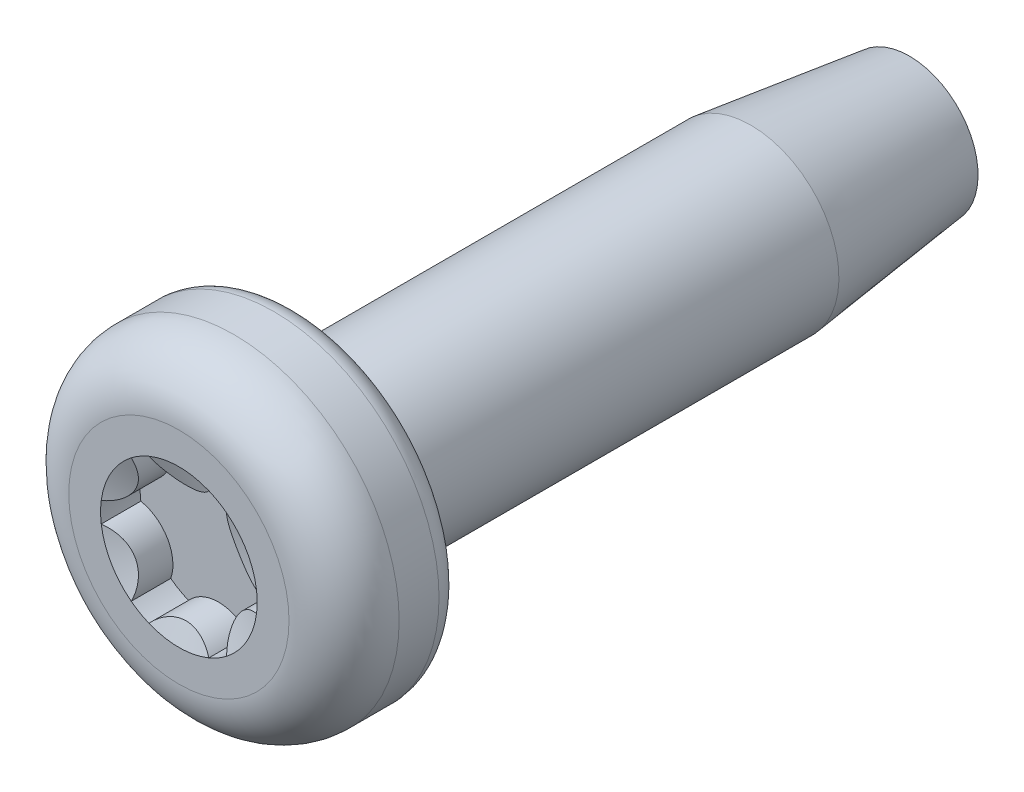
SolidWorks part; units mm, degrees
material "Alloy Steel"
ref_plane "Front" through (0, 0, 0) normal (0, 0, 1) x (1, 0, 0)
ref_plane "Top" through (0, 0, 0) normal (0, 1, 0) x (1, 0, 0)
ref_plane "Right" through (0, 0, 0) normal (1, 0, 0) x (0, 0, -1)
ref_axis "Central Axis" through (0, 0, -94.3109) along (0, 0, 1)
sketch "Sketch17" plane through (0, 0, 0) normal (1, 0, 0) x (0, 0, -1)
  line L1 (0, 0) -> (12.7, 0)
  line L2 (0, 0) -> (0, 1.8288)
  line L3 (0, 1.8288) -> (9.4082, 1.8288)
  line L4 (12.7, 0) -> (12.7, 1.4246)
  line L5 (11.6027, 1.5593) -> (10.5054, 1.6941)
  line L6 (10.5054, 1.6941) -> (10.5054, 1.8288) construction
  line L7 (11.6027, 1.5593) -> (12.7, 1.4246)
  line L8 (10.5054, 1.6941) -> (9.4082, 1.8288)
  line L9 (9.4082, 1.8288) -> (12.7, 1.8288) construction
  line L10 (12.7, 1.8288) -> (12.7, 1.4246) construction
  line L11 (12.7, 0) -> (13.8055, 0) construction
  line L12 (12.7, -1.778) -> (12.7, 1.778) construction
  point P5 (12.7, 1.778)
  point P16 (12.7, 0)
  dimension "Body Length" = 12.7
  dimension "D2" = 2.1946
  dimension "D1" = 7
  dimension "Decimal Equivilent" = 3.556
  dimension "Dia" = 3.6576
revolve "Revolve1" add sketch "Sketch17" angle 360 about L11
sketch "Sketch1" plane through (0, 0, 0) normal (0, 0, 1) x (1, 0, 0)
  circle A0 centre (0, 0) radius 3.429
  dimension "Head Dia" = 6.858
extrude "Extrude3" add sketch "Sketch1" along normal blind 2.4638
sketch "Sketch11" plane through (0, 0, 0) normal (1, 0, 0) x (0, 0, -1)
  line L2 (-2.4638, 3.429) -> (-2.4638, -3.429) construction
  line L4 (0, 3.429) -> (-2.4638, 3.429) construction
  line L5 (-1.3208, 3.429) -> (-0.4928, 3.429)
  line L6 (0, -3.429) -> (0, 3.429) construction
  line L7 (-2.4638, 3.429) -> (-2.4638, 2.286) construction
  line L8 (-2.4638, 1.143) -> (-2.4638, 0) construction
  line L9 (-2.4638, 2.286) -> (-2.4638, 1.143) construction
  line L10 (-2.4638, 2.286) -> (-2.7178, 2.286)
  line L11 (0, 0) -> (-2.4638, 0) construction
  line L12 (-2.7178, 2.286) -> (-2.7178, 3.683)
  line L13 (-2.7178, 3.683) -> (0.254, 3.683)
  line L14 (0.254, 3.683) -> (0.254, 2.9362)
  line L15 (0.254, 2.9362) -> (0, 2.9362)
  arc A0 (-2.4638, 2.286) -> (-1.3208, 3.429) centre (-1.3208, 2.286) cw
  arc A1 (-0.4928, 3.429) -> (0, 2.9362) centre (-0.4928, 2.9362) cw
  dimension "D1" = 0.4928
  dimension "D2" = 0.254
  dimension "D3" = 0.254
revolve "Cut-Revolve3" cut sketch "Sketch11" angle 360 about L11
sketch "Sketch12" plane through (0, 0, 2.4638) normal (0, 0, 1) x (1, 0, 0)
  line L0 (0, 0) -> (0, 1.2192) construction
  line L1 (0, 1.2192) -> (0, 1.6256) construction
  line L2 (0, 0) -> (-0.8128, 1.4078) construction
  line L3 (-0.8128, 1.4078) -> (0.8128, 1.4078) construction
  line L4 (0.8128, 1.4078) -> (0, 0) construction
  line L5 (0.6221, 1.5019) -> (0, 0) construction
  line L6 (0, 0) -> (0.8128, 1.4078) construction
  circle A0 centre (0, 0) radius 1.6256 construction
  circle A2 centre (0, 0) radius 1.4224 construction
  circle A3 centre (0, 0) radius 1.2192 construction
  arc A4 (0.8128, 1.4078) -> (0.6221, 1.5019) centre (0, 0) ccw
  arc A5 (-0.8128, 1.4078) -> (-0.6221, 1.5019) centre (0, 0) cw
  arc A6 (-0.6221, 1.5019) -> (0.6221, 1.5019) centre (0, 2.0451) ccw
  arc A7 (0.8128, 1.4078) -> (0.9896, 1.2897) centre (0, 0) cw
  arc A8 (0.9896, 1.2897) -> (1.6117, 0.2122) centre (1.7711, 1.0225) ccw
  arc A9 (1.6256, 0) -> (1.6117, 0.2122) centre (0, 0) ccw
  arc A10 (1.6256, 0) -> (1.6117, -0.2122) centre (0, 0) cw
  arc A11 (1.6117, -0.2122) -> (0.9896, -1.2897) centre (1.7711, -1.0225) ccw
  arc A12 (0.8128, -1.4078) -> (0.9896, -1.2897) centre (0, 0) ccw
  arc A13 (0.8128, -1.4078) -> (0.6221, -1.5019) centre (0, 0) cw
  arc A14 (0.6221, -1.5019) -> (-0.6221, -1.5019) centre (0, -2.0451) ccw
  arc A15 (-0.8128, -1.4078) -> (-0.6221, -1.5019) centre (0, 0) ccw
  arc A16 (-0.8128, -1.4078) -> (-0.9896, -1.2897) centre (0, 0) cw
  arc A17 (-0.9896, -1.2897) -> (-1.6117, -0.2122) centre (-1.7711, -1.0225) ccw
  arc A18 (-1.6256, 0) -> (-1.6117, -0.2122) centre (0, 0) ccw
  arc A19 (-1.6256, 0) -> (-1.6117, 0.2122) centre (0, 0) cw
  arc A20 (-1.6117, 0.2122) -> (-0.9896, 1.2897) centre (-1.7711, 1.0225) ccw
  arc A21 (-0.8128, 1.4078) -> (-0.9896, 1.2897) centre (0, 0) ccw
  point P4 (0, 1.4224)
  dimension "Torx Size" = 3.2512
  dimension "D1" = 2.4384
  dimension "D2" = 7.5
  dimension "D3" = 6
extrude "Cut-Extrude1" cut sketch "Sketch12" against normal blind 0.8213
sketch "Sketch25" plane through (0, 0, 2.4638) normal (0, 0, 1) x (1, 0, 0)
  circle A0 centre (0, 0) radius 1.6256
  circle A2 centre (0, 0) radius 1.6256 construction
extrude "Cut-Extrude7" cut sketch "Sketch25" against normal through all draft 70
sketch "Sketch19" plane through (0, 0, 0) normal (1, 0, 0) x (0, 0, -1)
  line L0 (6.35, 1.8288) -> (6.35, -1.8288) construction
  line L3 (0, 0) -> (12.7, 0) construction
  line L4 (12.7, 1.8288) -> (12.7, -1.8288) construction
  point P0 (-2.4638, 2.286)
  point P1 (0, 2.9362)
  point P2 (6.35, 0)
sketch "Sketch26" plane through (0, 0, 1.6425) normal (0, 0, 1) x (1, 0, 0)
  line L0 (0, 0) -> (1.1495, -1.1495) construction
  circle A0 centre (0, 0) radius 1.6256 construction
  point P0 (1.1495, -1.1495)
  dimension "D1" = 45
ref_axis "Center Axis 1" through (0, 0, 0) along (0, 0, -1)
split "Split1" [suppressed] bodies to split 157
sketch "Sketch23" [suppressed] plane through (0, 0, -12.7) normal (0, 0, -1) x (-1, 0, 0)
  circle A1 centre (0, 0) radius 1.4246
  circle A2 centre (0, 0) radius 1.4246
  dimension "D1" = 0
curve "Helix/Spiral1" [suppressed] pitch 1.3368 height 15.1638 turns 11.343
sketch "Sketch21" [suppressed] plane through (0, 0, 0) normal (1, 0, 0) x (0, 0, -1)
  line L0 (12.7, 1.8288) -> (13.97, 1.8288)
  line L1 (13.97, 1.8288) -> (13.6443, 1.0973)
  line L2 (13.6443, 1.0973) -> (13.0257, 1.0973)
  line L3 (13.0257, 1.0973) -> (12.7, 1.8288)
  dimension "D1" = 48
  dimension "D2" = 1.27
  dimension "D3" = 0.7315
sweep "Cut-Sweep1" [suppressed] cut profiles "Sketch21" path "Helix/Spiral1"
sketch "Sketch18" [suppressed] plane through (0, 0, 0) normal (0, 0, -1) x (-1, 0, 0)
  line L0 (0, 1.8288) -> (0, 0) construction
  line L1 (0, 0) -> (-1.5838, -0.9144) construction
  line L2 (0, 0) -> (1.5838, -0.9144) construction
  circle A0 centre (0, 0) radius 1.8288 construction
  arc A1 (-0.3658, 1.7308) -> (0.3658, 1.7308) centre (0, 1.0973) cw
  arc A2 (-1.6818, -0.5486) -> (-1.316, -1.1822) centre (-0.9503, -0.5486) ccw
  arc A3 (1.6818, -0.5486) -> (1.316, -1.1822) centre (0.9503, -0.5486) cw
  arc A4 (-0.3658, 1.7308) -> (-1.6818, -0.5486) centre (0.9504, -0.5487) ccw
  arc A5 (0.3658, 1.7308) -> (1.6818, -0.5486) centre (-0.9504, -0.5487) cw
  arc A6 (-1.316, -1.1822) -> (1.316, -1.1822) centre (0, 1.0974) ccw
  dimension "D3" = 0.7315
  dimension "D1" = 120
  dimension "D2" = 120
  dimension "D4" = 0.0001
extrude "Cut-Extrude3" [suppressed] cut sketch "Sketch18" along normal through all flip side to cut
combine bodies "Combine1" [suppressed] operation type add bodies to combine 158 148
equation "\"D1@Cut-Extrude1\"=\"Head Ht@Extrude3\"/3"
equation "\"D1@Sketch11\" = \"Head Ht@Extrude3\"/5"
equation "\"D3@Helix/Spiral1\" = \"Body Length@Sketch17\" + \"Head Ht@Extrude3\""
equation "\"D2@Sketch21\" = \"D4@Helix/Spiral1\" -  ( \"D4@Helix/Spiral1\" * .05 ) "
equation "\"D3@Sketch21\" = \"Dia@Sketch17\" * .2"
equation "\"D3@Sketch18\" = \"Dia@Sketch17\" * .2"
equation "\"D2@Sketch17\" = \"Dia@Sketch17\" * .6"
equation "\"D1@Sketch12\"=\"Torx Size@Sketch12\"*.75"
